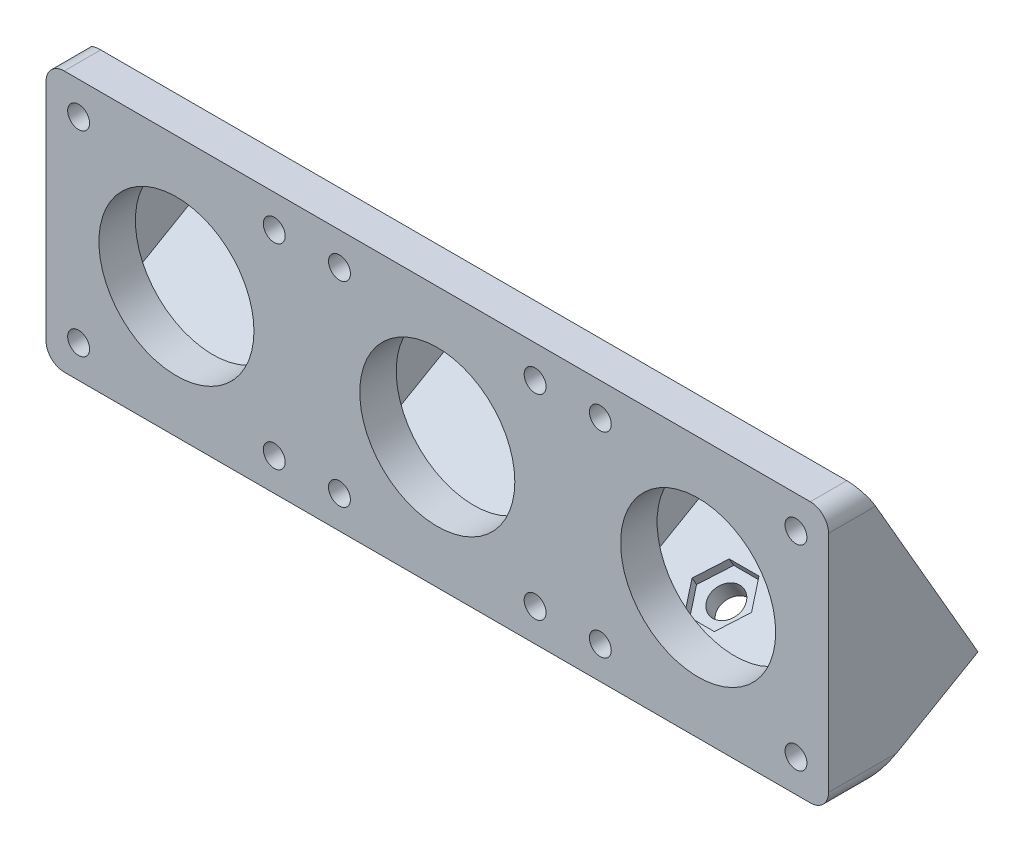
SolidWorks part; units mm, degrees
ref_plane "Front Plane" through (0, 0, 0) normal (0, 0, 1) x (1, 0, 0)
ref_plane "Top Plane" through (0, 0, 0) normal (0, 1, 0) x (1, 0, 0)
ref_plane "Right Plane" through (0, 0, 0) normal (1, 0, 0) x (0, 0, -1)
sketch "Sketch1" plane through (0, 0, 0) normal (0, 0, 1) x (1, 0, 0)
  line L0 (-28.6, 0) -> (16.7561, 45.3561) construction
  line L1 (-42.9, -14.3) -> (42.9, -14.3)
  line L2 (-42.9, -14.3) -> (-42.9, 14.3)
  line L3 (-42.9, 14.3) -> (42.9, 14.3)
  line L4 (42.9, -14.3) -> (42.9, 14.3)
  line L7 (-14.3, 14.3) -> (71.5, 14.3) [skipped]
  line L8 (14.3, 14.3) -> (100.1, 14.3) [skipped]
  circle A0 centre (-28.6, 0) radius 8.5
  circle A1 centre (0, 0) radius 8.5
  circle A2 centre (28.6, 0) radius 8.5
  circle A3 centre (-17.875, 10.725) radius 1.2
  circle A4 centre (-17.875, -10.725) radius 1.2
  circle A5 centre (-39.325, -10.725) radius 1.2
  circle A6 centre (-39.325, 10.725) radius 1.2
  circle A7 centre (-10.725, 10.725) radius 1.2
  circle A8 centre (10.725, 10.725) radius 1.2
  circle A9 centre (10.725, -10.725) radius 1.2
  circle A10 centre (-10.725, -10.725) radius 1.2
  circle A11 centre (17.875, 10.725) radius 1.2
  circle A12 centre (39.325, 10.725) radius 1.2
  circle A13 centre (39.325, -10.725) radius 1.2
  circle A14 centre (17.875, -10.725) radius 1.2
  point P11 (0, -14.3)
  point P12 (-42.9, 0)
  point P26 (-28.6, 0)
  dimension "D3" = 28.6
  dimension "D5" = 17
  dimension "D6" = 2.4
  dimension "D1" = 28.6
  dimension "D2" = 85.8
  dimension "D4" = 28.6
  dimension "D7" = 10.725
  dimension "D8" = 45
  dimension "D10" = 3
  dimension "D9" = 4
extrude "Boss-Extrude1" add sketch "Sketch1" along normal blind 4
sketch "Sketch2" plane through (42.9, 0, 0) normal (1, 0, 0) x (0, 0, -1)
  line L0 (0, -14.3) -> (12.3842, -7.15)
  line L1 (12.3842, -7.15) -> (0, 14.3)
  line L2 (0, 14.3) -> (0, -14.3)
  dimension "D1" = 90
  dimension "D2" = 60
extrude "Boss-Extrude2" add sketch "Sketch2" against normal blind 2
pattern_linear "LPattern1" count 4 spacing 27.9333 along (-1, 0, 0) of "Boss-Extrude2"
sketch "Sketch3" plane through (40.9, 0, 0) normal (-1, 0, 0) x (0, 0, 1)
  line L0 (0, -14.3) -> (-12.3842, -7.15)
  line L1 (-12.3842, -7.15) -> (-10.8842, -4.5519)
  line L2 (-12.3842, -7.15) -> (0, 14.3) construction
  line L3 (-10.8842, -4.5519) -> (0, -10.8359)
  line L4 (0, 14.3) -> (0, -14.3) construction
  line L5 (0, -10.8359) -> (0, -14.3)
  dimension "D1" = 3
extrude "Boss-Extrude5" add sketch "Sketch3" along normal up to surface (81.8 mm away) up to face at (-40.9, -2.3833, -4.1281)
sketch "Sketch4" plane through (0, 0, 4) normal (0, 0, 1) x (1, 0, 0)
  circle A0 centre (-39.325, -10.725) radius 1.2 construction
  circle A1 centre (-17.875, -10.725) radius 1.2 construction
  circle A2 centre (-10.725, -10.725) radius 1.2 construction
  circle A3 centre (10.725, -10.725) radius 1.2 construction
  circle A4 centre (17.875, -10.725) radius 1.2 construction
  circle A5 centre (39.325, -10.725) radius 1.2 construction
  circle A6 centre (-39.325, -10.725) radius 1.2
  circle A7 centre (-17.875, -10.725) radius 1.2
  circle A8 centre (-10.725, -10.725) radius 1.2
  circle A9 centre (10.725, -10.725) radius 1.2
  circle A10 centre (17.875, -10.725) radius 1.2
  circle A11 centre (39.325, -10.725) radius 1.2
extrude "Cut-Extrude1" cut sketch "Sketch4" against normal through all
fillet "Fillet1" radius 2 4 edges at (42.9, 14.3, 2) (42.9, -14.3, 2) (-42.9, -14.3, 2) (-42.9, 14.3, 2)
sketch "Sketch8" plane through (0, -8.1269, -4.6921) normal (0, 0.866, 0.5) x (1, 0, 0)
  line L0 (0, 0) -> (0, 50000) construction
  line L1 (-25.762, 0) -> (-24.131, 2.825)
  line L2 (25.762, 0) -> (24.131, 2.825)
  line L3 (24.131, 2.825) -> (20.869, 2.825)
  line L4 (20.869, 2.825) -> (19.238, 0)
  line L5 (19.238, 0) -> (20.869, -2.825)
  line L6 (20.869, -2.825) -> (24.131, -2.825)
  line L7 (24.131, -2.825) -> (25.762, 0)
  line L8 (-24.131, 2.825) -> (-20.869, 2.825)
  line L9 (-20.869, 2.825) -> (-19.238, 0)
  line L10 (-19.238, 0) -> (-20.869, -2.825)
  line L11 (-20.869, -2.825) -> (-24.131, -2.825)
  line L12 (-24.131, -2.825) -> (-25.762, 0)
  circle A0 centre (22.5, 0) radius 1.7
  circle A1 centre (-22.5, 0) radius 1.7
  circle A2 centre (22.5, 0) radius 2.825 construction
  dimension "D1" = 3.4
  dimension "D3" = 5.65
  dimension "D2" = 45
extrude "Cut-Extrude3" cut sketch "Sketch8" against normal blind 1
extrude "Cut-Extrude4" cut sketch "Sketch8<2>" against normal through all contours A0 | A1 region at (22.5, -8.1269, -4.6921) region at (-22.5, -8.1269, -4.6921)
sketch "Sketch8<2>" plane through (0, -8.1269, -4.6921) normal (0, 0.866, 0.5) x (1, 0, 0) same geometry as "Sketch8"
